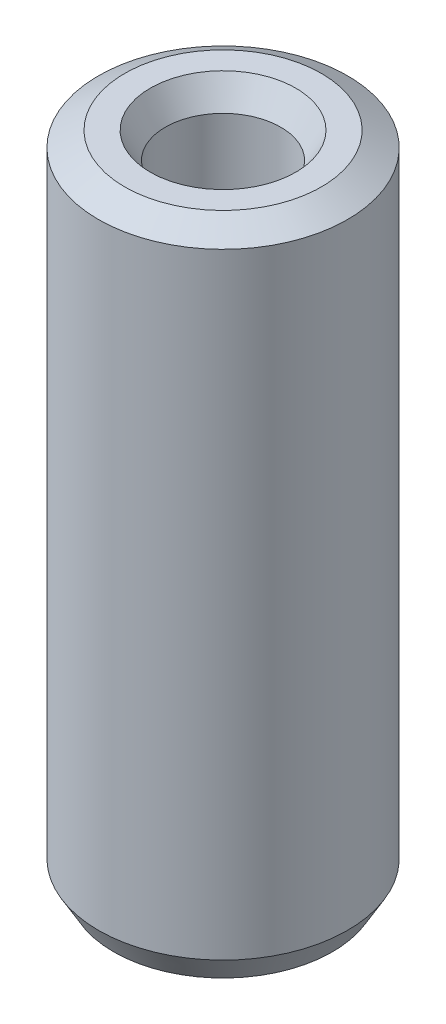
SolidWorks part; units mm, degrees
ref_plane "Front Plane" through (0, 0, 0) normal (0, 0, 1) x (1, 0, 0)
ref_plane "Top Plane" through (0, 0, 0) normal (0, 1, 0) x (1, 0, 0)
ref_plane "Right Plane" through (0, 0, 0) normal (1, 0, 0) x (0, 0, -1)
sketch "Sketch1" plane through (0, 0, 0) normal (0, 1, 0) x (1, 0, 0)
  circle A0 centre (0, 0) radius 17.5
  dimension "SLEEVE_OD" = 35
extrude "Boss-Extrude1" add sketch "Sketch1" along normal blind 92.2959
sketch "Sketch2" plane through (0, 0, 0) normal (0, 1, 0) x (1, 0, 0)
  circle A0 centre (0, 0) radius 8.1047
  dimension "BORE_D" = 16.2094
extrude "Cut-Extrude1" cut sketch "Sketch2" along normal through all
chamfer "Chamfer1" distance 2.1258 angle 60 4 edges at (0, 92.2959, 8.1047) (0, 0, 8.1047) (0, 0, 17.5) (0, 92.2959, 17.5) first distance on face at (0, 92.2959, 8.1047) first distance on face at (0, 0, 8.1047) first distance on face at (0, 92.2959, 17.5)
